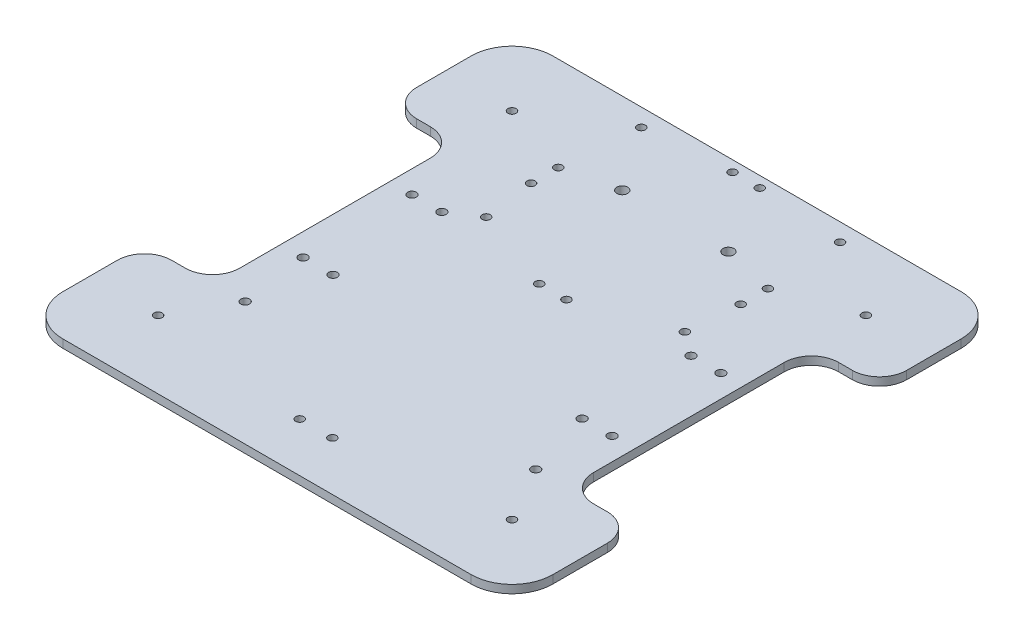
SolidWorks part; units mm, degrees
ref_plane "Спереди" through (0, 0, 0) normal (0, 0, 1) x (1, 0, 0)
ref_plane "Сверху" through (0, 0, 0) normal (0, 1, 0) x (1, 0, 0)
ref_plane "Справа" through (0, 0, 0) normal (1, 0, 0) x (0, 0, -1)
sketch "Sketch1" plane through (0, 0, 0) normal (0, 1, 0) x (1, 0, 0)
  line L1 (-90, 90) -> (90, 90)
  line L2 (-90, 90) -> (-90, -90)
  line L3 (-90, -90) -> (90, -90)
  line L4 (90, 90) -> (90, -90)
  line L5 (-90, 90) -> (90, -90) construction
  line L6 (-90, -90) -> (90, 90) construction
  point P0 (0, 0)
  dimension "D1" = 180
  dimension "D2" = 180
extrude "Boss-Extrude1" add sketch "Sketch1" along normal blind 3
fillet "Fillet1" radius 15 4 edges at (-90, 1.5, -90) (90, 1.5, -90) (-90, 1.5, 90) (90, 1.5, 90)
sketch "Sketch2" plane through (0, 3, 0) normal (0, 1, 0) x (1, 0, 0)
  line L0 (0, 0) -> (-77.5, 0) construction
  line L1 (2.75, 0) -> (-2.75, 0) construction
  line L2 (-90, 75) -> (-90, -75) construction
  line L3 (-90, 45) -> (-65, 45)
  line L4 (-90, 45) -> (-90, -45)
  line L5 (-90, -45) -> (-65, -45)
  line L6 (-65, 45) -> (-65, -45)
  line L7 (-90, 45) -> (-65, -45) construction
  line L8 (-90, -45) -> (-65, 45) construction
  line L9 (0, 0) -> (0, 45) construction
  line L10 (90, -45) -> (65, 45) construction
  line L11 (90, 45) -> (65, -45) construction
  line L12 (65, 45) -> (65, -45)
  line L13 (90, -45) -> (65, -45)
  line L14 (90, 45) -> (90, -45)
  line L15 (90, 45) -> (65, 45)
  circle A0 centre (-56.75, 20) radius 1.6
  circle A1 centre (-45.75, 20) radius 1.6
  circle A2 centre (-56.75, -20) radius 1.6
  circle A3 centre (-45.75, -20) radius 1.6
  circle A4 centre (45.75, 20) radius 1.6
  circle A5 centre (56.75, 20) radius 1.6
  circle A6 centre (45.75, -20) radius 1.6
  circle A7 centre (56.75, -20) radius 1.6
  dimension "D1" = 25
  dimension "D2" = 90
extrude "Cut-Extrude2" cut sketch "Sketch2" against normal through all
fillet "Fillet2" radius 10 8 edges at (-65, 1.5, 45) (-65, 1.5, -45) (65, 1.5, -45) (65, 1.5, 45) (90, 1.5, -45) (90, 1.5, 45) (-90, 1.5, 45) (-90, 1.5, -45)
hole_wizard "Диаметр отверстия Ø3.0 (3)1" positions "Эскиз2" profile "Эскиз1" hole size "Ø3.0" standard "Ansi Metric" end condition up to next
sketch "Эскиз2" plane through (0, 3, 0) normal (0, 1, 0) x (1, 0, 0)
  line L7 (-65, -65) -> (-65, 65) construction
  line L9 (65, 65) -> (65, -65) construction
  line L11 (-90, 65) -> (-65, 65) construction
  line L12 (-90, 75) -> (-90, 55) construction
  line L13 (-65, 65) -> (65, 65) construction
  line L14 (65, 65) -> (90, 65) construction
  line L15 (90, 55) -> (90, 75) construction
  line L17 (90, -65) -> (65, -65) construction
  line L18 (90, -75) -> (90, -55) construction
  line L19 (65, -65) -> (-65, -65) construction
  line L20 (-65, -65) -> (-90, -65) construction
  line L21 (-90, -55) -> (-90, -75) construction
  line L22 (-65, 65) -> (-65, 90) construction
  line L23 (75, 90) -> (-75, 90) construction
  point P15 (-65, -65)
  point P16 (-65, 65)
  point P19 (65, 65)
  point P20 (65, -65)
sketch "Эскиз1" plane through (-65, 3, 65) normal (1, 0, 0) x (0, 0, 1)
  line L0 (0, 0) -> (0, 3)
  line L1 (0, 3) -> (1.5, 3)
  line L2 (1.5, 3) -> (1.5, 0)
  line L5 (1.5, 0) -> (0, 0)
  line L11 (0, -6.35) -> (0, 107.95) construction
  dimension "Диаметр сквозного отверстия" = 3
  dimension "Глубина сквозного отверстия" = 3
hole_wizard "Диаметр отверстия Ø3.0 (3)2" positions "Эскиз4" profile "Эскиз3" hole size "Ø3.0" standard "Ansi Metric" end condition up to next
sketch "Эскиз4" plane through (0, 3, 0) normal (0, 1, 0) x (1, 0, 0)
  line L0 (90, 65) -> (38.5, 65) construction
  line L1 (90, 55) -> (90, 75) construction
  line L2 (38.5, 65) -> (-38.5, 65) construction
  line L3 (-38.5, 65) -> (-90, 65) construction
  line L4 (-90, 75) -> (-90, 55) construction
  line L12 (-38.5, 15) -> (-5, 15) construction
  line L13 (-5, 15) -> (5, 15) construction
  line L14 (5, 15) -> (38.5, 15) construction
  line L16 (38.5, 86) -> (5, 86) construction
  line L17 (5, 86) -> (-5, 86) construction
  line L18 (-5, 86) -> (-38.5, 86) construction
  line L20 (38.5, 15) -> (38.5, 45.5) construction
  line L21 (38.5, 45.5) -> (38.5, 55.5) construction
  line L22 (38.5, 55.5) -> (38.5, 86) construction
  line L24 (-38.5, 86) -> (-38.5, 55.5) construction
  line L25 (-38.5, 55.5) -> (-38.5, 45.5) construction
  line L26 (-38.5, 45.5) -> (-38.5, 15) construction
  line L28 (75, 90) -> (-75, 90) construction
  point P63 (-5, 15)
  point P66 (-38.5, 45.5)
  point P69 (-38.5, 55.5)
  point P72 (5, 15)
  point P75 (38.5, 45.5)
  point P78 (38.5, 55.5)
  point P81 (5, 86)
  point P84 (-5, 86)
  dimension "D1" = 10
  dimension "D2" = 71
  dimension "D3" = 77
  dimension "D4" = 4
sketch "Эскиз3" plane through (-5, 3, -15) normal (1, 0, 0) x (0, 0, 1)
  line L0 (0, 0) -> (0, 3)
  line L1 (0, 3) -> (1.5, 3)
  line L2 (1.5, 3) -> (1.5, 0)
  line L5 (1.5, 0) -> (0, 0)
  line L11 (0, -6.35) -> (0, 107.95) construction
  dimension "Диаметр сквозного отверстия" = 3
  dimension "Глубина сквозного отверстия" = 3
hole_wizard "Диаметр отверстия Ø4.0 (4)1" positions "Эскиз6" profile "Эскиз5" hole size "Ø4.0" standard "Ansi Metric" end condition up to next
sketch "Эскиз6" plane through (0, 3, 0) normal (0, 1, 0) x (1, 0, 0)
  line L0 (0, 90) -> (0, 60) construction
  line L1 (75, 90) -> (-75, 90) construction
  line L2 (0, 60) -> (0, -90) construction
  line L3 (-75, -90) -> (75, -90) construction
  line L5 (-19.5, 60) -> (19.5, 60) construction
  point P1 (-19.5, 60)
  point P20 (19.5, 60)
  dimension "D1" = 39
  dimension "D2" = 30
sketch "Эскиз5" plane through (-19.5, 3, -60) normal (1, 0, 0) x (0, 0, 1)
  line L0 (0, 0) -> (0, 3)
  line L1 (0, 3) -> (2, 3)
  line L2 (2, 3) -> (2, 0)
  line L5 (2, 0) -> (0, 0)
  line L11 (0, -6.35) -> (0, 107.95) construction
  dimension "Диаметр сквозного отверстия" = 4
  dimension "Глубина сквозного отверстия" = 3
sketch "Sketch3" plane through (0, 3, 0) normal (0, 1, 0) x (1, 0, 0)
  line L0 (0, -90) -> (0, -72) construction
  line L1 (-75, -90) -> (75, -90) construction
  line L2 (0, -72) -> (-6, -72) construction
  circle A0 centre (-6, -72) radius 1.5
  circle A1 centre (6, -72) radius 1.5
  circle A2 centre (53.3716, -44.65) radius 1.6
  circle A3 centre (-53.3716, -44.65) radius 1.6
  arc A4 (-52.7899, -46.1405) -> (-54.9533, -44.8915) centre (-53.3716, -44.65) ccw construction
  arc A5 (54.9533, -44.8915) -> (52.7899, -46.1405) centre (53.3716, -44.65) ccw construction
  dimension "D2" = 3
  dimension "D1" = 18
  dimension "D3" = 12
extrude "Cut-Extrude3" cut sketch "Sketch3" against normal through all
sketch "Sketch4" plane through (0, 3, 0) normal (0, 1, 0) x (1, 0, 0)
  circle A0 centre (-36, 83.5) radius 1.5
  circle A1 centre (37, 83.5) radius 1.5
  circle A2 centre (37, 26.5) radius 1.5
  circle A3 centre (-36, 26.5) radius 1.5
  circle A4 centre (-36, 26.5) radius 1.5 construction
  circle A5 centre (37, 26.5) radius 1.5 construction
  circle A7 centre (37, 83.5) radius 1.5 construction
  circle A8 centre (-36, 83.5) radius 1.5 construction
extrude "Cut-Extrude4" cut sketch "Sketch4" against normal through all
